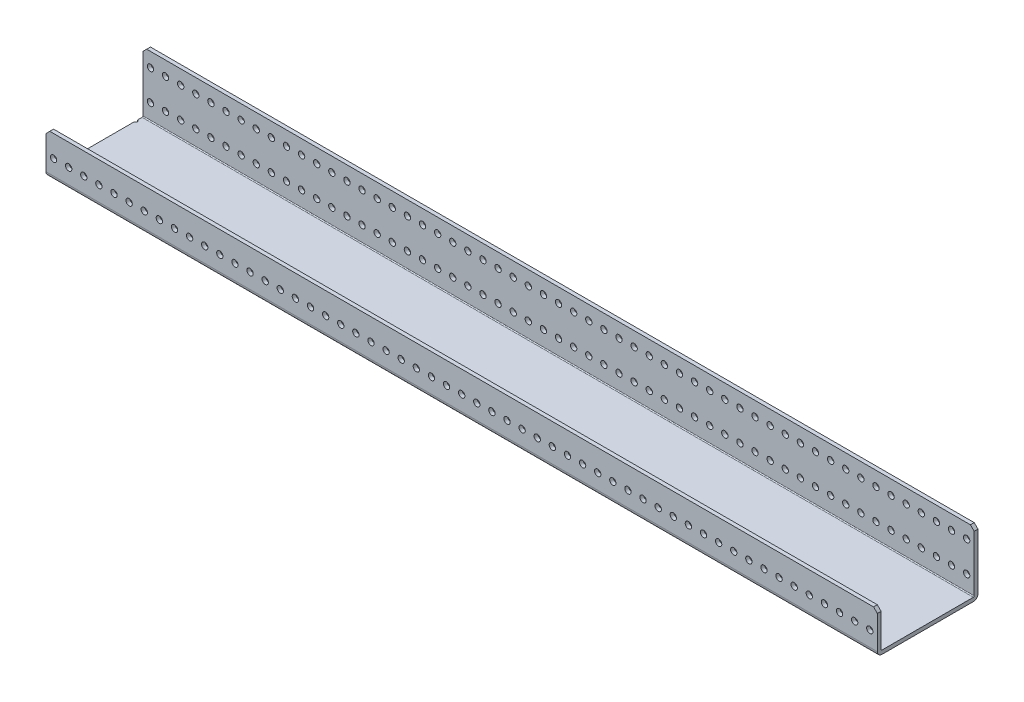
SolidWorks part; units mm, degrees
ref_plane "Front Plane" through (0, 0, 0) normal (0, 0, 1) x (1, 0, 0)
ref_plane "Top Plane" through (0, 0, 0) normal (0, 1, 0) x (1, 0, 0)
ref_plane "Right Plane" through (0, 0, 0) normal (1, 0, 0) x (0, 0, -1)
ref_plane "Plane4" through (0, 57.8164, 0) normal (0, 1, 0) x (1, 0, 0)
sketch "Sketch1" plane through (0, 57.8164, 0) normal (0, 1, 0) x (1, 0, 0)
  line L0 (602.398, -145.5605) -> (602.398, -60.9785)
  line L1 (602.398, -60.9785) -> (-96.102, -60.9785)
  line L2 (-96.102, -60.9785) -> (-96.102, -145.5605)
  line L3 (-96.102, -145.5605) -> (602.398, -145.5605)
  dimension "D1" = 698.5
extrude "Boss-Extrude1" add sketch "Sketch1" against normal blind 34.925
sketch "Sketch2" plane through (602.398, 0, 0) normal (1, 0, 0) x (0, 0, -1)
  line L0 (-60.9785, 57.8164) -> (-142.3855, 57.8164)
  line L1 (-142.3855, 57.8164) -> (-142.3855, 26.0664)
  line L2 (-142.3855, 26.0664) -> (-60.9785, 26.0664)
  line L3 (-60.9785, 26.0664) -> (-60.9785, 57.8164)
extrude "Cut-Extrude1" cut sketch "Sketch2" against normal through all
sketch "Sketch3" plane through (0, 26.0664, 0) normal (0, 1, 0) x (-1, 0, 0)
  line L0 (96.102, 60.9785) -> (-602.398, 60.9785)
  line L1 (-602.398, 60.9785) -> (-602.398, 64.1535)
  line L2 (-602.398, 64.1535) -> (96.102, 64.1535)
  line L3 (96.102, 64.1535) -> (96.102, 60.9785)
  line L5 (-602.398, 142.3855) -> (-602.398, 60.9785) construction
  line L6 (96.102, 142.3855) -> (96.102, 60.9785) construction
extrude "Boss-Extrude2" add sketch "Sketch3" along normal blind 50.8
hole_wizard "M2 Clearance Hole1" positions "Sketch5" profile "Sketch4" hole size "M2" standard "ANSI Metric" end condition through all
sketch "Sketch5" plane through (0, 26.0664, 0) normal (0, 1, 0) x (1, 0, 0)
  point P0 (-96.102, -136.5435)
  point P1 (-96.102, -69.9955)
sketch "Sketch4" plane through (-96.102, 26.0664, 136.5435) normal (1, 0, 0) x (0, 0, 1)
  line L0 (0, 0) -> (0, 3.175)
  line L1 (0, 3.175) -> (1.27, 3.175)
  line L2 (1.27, 3.175) -> (1.27, 0)
  line L5 (1.27, 0) -> (0, 0)
  line L11 (0, -6.35) -> (0, 107.95) construction
  dimension "Thru Hole Dia." = 2.54
  dimension "Thru Hole Depth" = 3.175
hole_wizard "M5 Clearance Hole1" positions "Sketch7" profile "Sketch6" hole size "M5" standard "ANSI Metric" end condition through all
sketch "Sketch7" plane through (0, 0, 60.9785) normal (0, 0, -1) x (-1, 0, 0)
  point P0 (-469.048, 64.9284)
  point P1 (-481.748, 64.9284)
  point P2 (-469.048, 39.5284)
  point P3 (-481.748, 39.5284)
  point P4 (-456.348, 39.5284)
  point P5 (-443.648, 39.5284)
  point P6 (-430.948, 39.5284)
  point P7 (-418.248, 39.5284)
  point P8 (-405.548, 39.5284)
  point P9 (-392.848, 39.5284)
  point P10 (-380.148, 39.5284)
  point P11 (-367.448, 39.5284)
  point P12 (-354.748, 39.5284)
  point P13 (-342.048, 39.5284)
  point P14 (-329.348, 39.5284)
  point P15 (-316.648, 39.5284)
  point P16 (-303.948, 39.5284)
  point P17 (-291.248, 39.5284)
  point P18 (-278.548, 39.5284)
  point P19 (-265.848, 39.5284)
  point P20 (-253.148, 39.5284)
  point P21 (-240.448, 39.5284)
  point P22 (-227.748, 39.5284)
  point P23 (-215.048, 39.5284)
  point P24 (-202.348, 39.5284)
  point P25 (-189.648, 39.5284)
  point P26 (-176.948, 39.5284)
  point P27 (-164.248, 39.5284)
  point P28 (-151.548, 39.5284)
  point P29 (-138.848, 39.5284)
  point P30 (-126.148, 39.5284)
  point P31 (-113.448, 39.5284)
  point P32 (-100.748, 39.5284)
  point P33 (-88.048, 39.5284)
  point P34 (-75.348, 39.5284)
  point P35 (-62.648, 39.5284)
  point P36 (-49.948, 39.5284)
  point P37 (-37.248, 39.5284)
  point P38 (-24.548, 39.5284)
  point P39 (-11.848, 39.5284)
  point P40 (0.852, 39.5284)
  point P41 (13.552, 39.5284)
  point P42 (26.252, 39.5284)
  point P43 (38.952, 39.5284)
  point P44 (51.652, 39.5284)
  point P45 (64.352, 39.5284)
  point P46 (77.052, 39.5284)
  point P47 (89.752, 39.5284)
  point P48 (-456.348, 64.9284)
  point P49 (-443.648, 64.9284)
  point P50 (-430.948, 64.9284)
  point P51 (-418.248, 64.9284)
  point P52 (-405.548, 64.9284)
  point P53 (-392.848, 64.9284)
  point P54 (-380.148, 64.9284)
  point P55 (-367.448, 64.9284)
  point P56 (-354.748, 64.9284)
  point P57 (-342.048, 64.9284)
  point P58 (-329.348, 64.9284)
  point P59 (-316.648, 64.9284)
  point P60 (-303.948, 64.9284)
  point P61 (-291.248, 64.9284)
  point P62 (-278.548, 64.9284)
  point P63 (-265.848, 64.9284)
  point P64 (-253.148, 64.9284)
  point P65 (-240.448, 64.9284)
  point P66 (-227.748, 64.9284)
  point P67 (-215.048, 64.9284)
  point P68 (-202.348, 64.9284)
  point P69 (-189.648, 64.9284)
  point P70 (-176.948, 64.9284)
  point P71 (-164.248, 64.9284)
  point P72 (-151.548, 64.9284)
  point P73 (-138.848, 64.9284)
  point P74 (-126.148, 64.9284)
  point P75 (-113.448, 64.9284)
  point P76 (-100.748, 64.9284)
  point P77 (-88.048, 64.9284)
  point P78 (-75.348, 64.9284)
  point P79 (-62.648, 64.9284)
  point P80 (-49.948, 64.9284)
  point P81 (-37.248, 64.9284)
  point P82 (-24.548, 64.9284)
  point P83 (-11.848, 64.9284)
  point P84 (0.852, 64.9284)
  point P85 (13.552, 64.9284)
  point P86 (26.252, 64.9284)
  point P87 (38.952, 64.9284)
  point P88 (51.652, 64.9284)
  point P89 (64.352, 64.9284)
  point P90 (77.052, 64.9284)
  point P91 (89.752, 64.9284)
  point P97 (-494.448, 64.9284)
  point P98 (-494.448, 39.5284)
  point P99 (-507.148, 64.9284)
  point P100 (-507.148, 39.5284)
  point P101 (-519.848, 64.9284)
  point P102 (-519.848, 39.5284)
  point P103 (-532.548, 64.9284)
  point P104 (-532.548, 39.5284)
  point P105 (-545.248, 64.9284)
  point P106 (-545.248, 39.5284)
  point P107 (-557.948, 64.9284)
  point P108 (-557.948, 39.5284)
  point P109 (-570.648, 64.9284)
  point P110 (-570.648, 39.5284)
  point P111 (-583.348, 64.9284)
  point P112 (-583.348, 39.5284)
  point P113 (-596.048, 64.9284)
  point P114 (-596.048, 39.5284)
  dimension "D1" = 10
sketch "Sketch6" plane through (469.048, 64.9284, 60.9785) normal (1, 0, 0) x (0, 1, 0)
  line L0 (0, 0) -> (0, 84.582)
  line L1 (0, 84.582) -> (2.667, 84.582)
  line L2 (2.667, 84.582) -> (2.667, 0)
  line L5 (2.667, 0) -> (0, 0)
  line L11 (0, -6.35) -> (0, 107.95) construction
  dimension "Thru Hole Dia." = 5.334
  dimension "Thru Hole Depth" = 84.582
chamfer "Chamfer1" distance 3.175 angle 45 4 edges at (602.398, 76.8664, 62.566) (-96.102, 57.8164, 143.973) (602.398, 57.8164, 143.973) (-96.102, 76.8664, 62.566)
fillet "Fillet1" radius 0.762 2 edges at (253.148, 26.0664, 64.1535) (253.148, 26.0664, 142.3855) tangent propagation no
fillet "Fillet2" radius 3.937 2 edges at (253.148, 22.8914, 145.5605) (253.148, 22.8914, 60.9785) tangent propagation no
